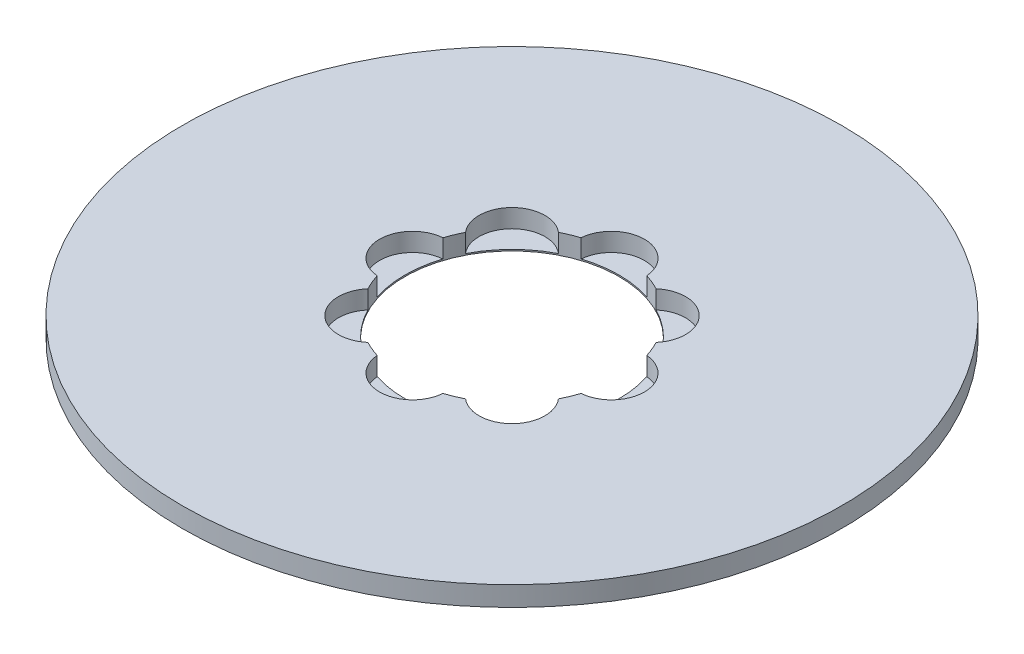
SolidWorks part; units mm, degrees
ref_plane "Front Plane" through (0, 0, 0) normal (0, 0, 1) x (1, 0, 0)
ref_plane "Top Plane" through (0, 0, 0) normal (0, 1, 0) x (1, 0, 0)
ref_plane "Right Plane" through (0, 0, 0) normal (1, 0, 0) x (0, 0, -1)
sketch "Sketch1" plane through (0, 0, 0) normal (0, 1, 0) x (1, 0, 0)
  circle A0 centre (0, 0) radius 100
  dimension "FLANGE_OD" = 200
extrude "Boss-Extrude1" add sketch "Sketch1" along normal blind 6
sketch "Sketch2" plane through (0, 0, 0) normal (0, 1, 0) x (1, 0, 0)
  circle A0 centre (0, 0) radius 32.5
  dimension "BORE_D" = 65
extrude "Cut-Extrude1" cut sketch "Sketch2" along normal through all
sketch "Sketch3" plane through (0, 6, 0) normal (0, 1, 0) x (1, 0, 0)
  circle A0 centre (0, 0) radius 30.1695 construction
  circle A1 centre (-30.1695, 0) radius 10
  dimension "BOLT_D" = 20
  dimension "BOLT_PCD" = 60.339
extrude "Cut-Extrude2" cut sketch "Sketch3" against normal blind 5.5797
pattern_circular "CirPattern1" count 8 over 360 about axis through (0, 0, 0) along (0, 1, 0) of "Cut-Extrude2"
